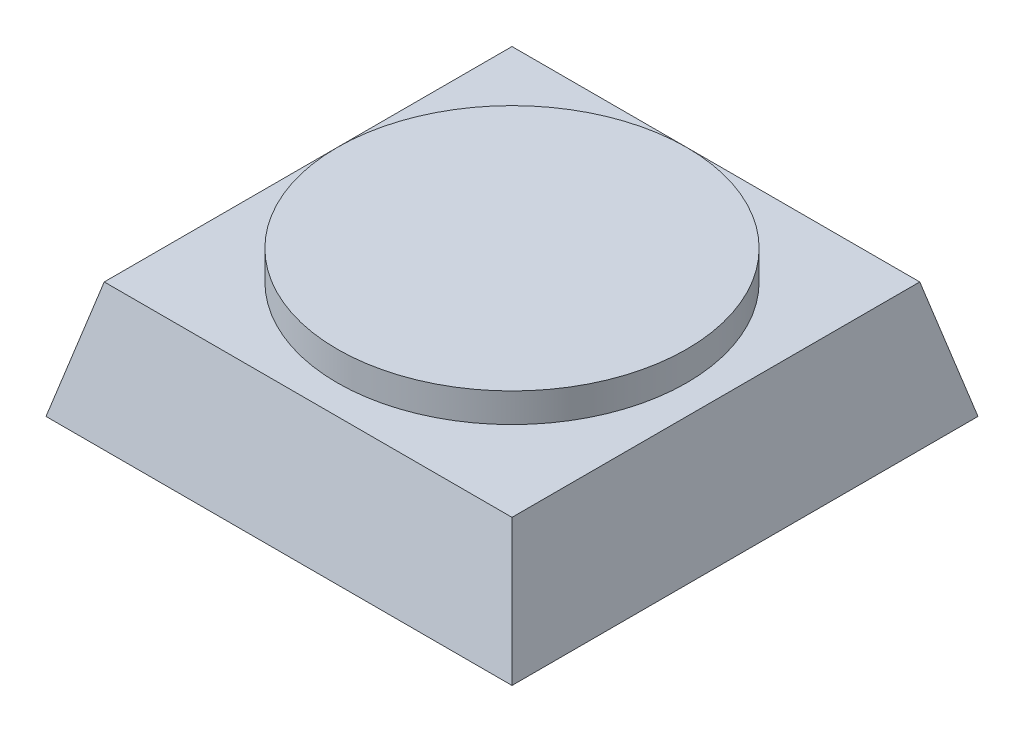
SolidWorks part; units mm, degrees
ref_plane "Спереди" through (0, 0, 0) normal (0, 0, 1) x (1, 0, 0)
ref_plane "Сверху" through (0, 0, 0) normal (0, 1, 0) x (1, 0, 0)
ref_plane "Сбоку" through (0, 0, 0) normal (1, 0, 0) x (0, 0, -1)
sketch "Эскиз1" plane through (0, 0, 0) normal (0, 1, 0) x (1, 0, 0)
  line L1 (-40, -40) -> (40, -40)
  line L2 (-40, -40) -> (-40, 40)
  line L3 (-40, 40) -> (40, 40)
  line L4 (40, -40) -> (40, 40)
  line L5 (-40, -40) -> (40, 40) construction
  line L6 (-40, 40) -> (40, -40) construction
  point P0 (0, 0)
  dimension "D1" = 80
  dimension "D2" = 80
extrude "Бобышка-Вытянуть1" add sketch "Эскиз1" along normal blind 20
sketch "Эскиз2" plane through (0, 20, 0) normal (0, 1, 0) x (1, 0, 0)
  circle A0 centre (0, 0) radius 30
  dimension "D1" = 60
extrude "Бобышка-Вытянуть2" add sketch "Эскиз2" along normal blind 5
chamfer "Фаска1" distance 20 distance2 5 4 edges at (40, 20, 0) (0, 20, -40) (-40, 20, 0) (0, 20, 40) first distance on face at (40, 10, 0) first distance on face at (0, 10, -40) first distance on face at (-40, 10, 0) first distance on face at (0, 10, 40)
